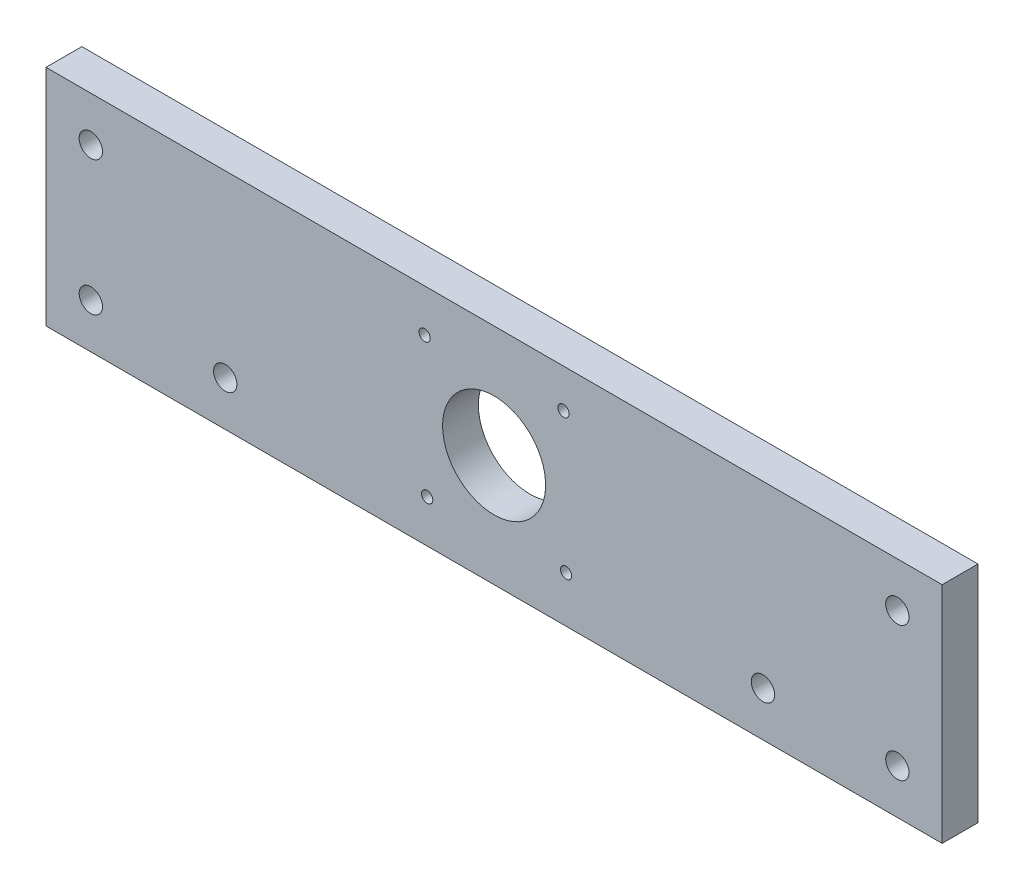
SolidWorks part; units mm, degrees
ref_plane "Ön Düzlem" through (0, 0, 0) normal (0, 0, 1) x (1, 0, 0)
ref_plane "Üst Düzlem" through (0, 0, 0) normal (0, 1, 0) x (1, 0, 0)
ref_plane "Sağ Düzlem" through (0, 0, 0) normal (1, 0, 0) x (0, 0, -1)
sketch "Çizim1" plane through (0, 0, 0) normal (0, 0, 1) x (1, 0, 0)
  line L1 (-88.1446, 49.1848) -> (111.8554, 49.1848)
  line L2 (-88.1446, 49.1848) -> (-88.1446, -0.8152)
  line L3 (-88.1446, -0.8152) -> (111.8554, -0.8152)
  line L4 (111.8554, 49.1848) -> (111.8554, -0.8152)
  circle A3 centre (-78.1446, 39.1848) radius 4.0251
  circle A4 centre (101.8554, 39.1848) radius 4.0251
  circle A5 centre (101.8554, 9.1848) radius 4.0251
  circle A6 centre (-78.1446, 9.1848) radius 4.0251
  dimension "D3" = 10
  dimension "D4" = 10
  dimension "D5" = 2
  dimension "D6" = 2
  dimension "D1" = 200
  dimension "D2" = 50
extrude "Yükseklik-Ekstrüzyon1" add sketch "Çizim1" along normal blind 8 contours L2 L1 L4 L3
hole_wizard "M5 Helisarmal için Zıvana matkabı1" positions "Çizim3" profile "Çizim4" hole size "M5x0.8" standard "ANSI Metric" end condition up to next
sketch "Çizim3" plane through (0, 0, 0) normal (0, 0, -1) x (-1, 0, 0)
  point P0 (-101.8554, 39.1848)
  point P3 (-101.8554, 9.1848)
  point P6 (78.1446, 9.1848)
  point P9 (78.1446, 39.1848)
sketch "Çizim4" plane through (101.8554, 39.1848, 0) normal (1, 0, 0) x (0, 1, 0)
  line L0 (0, 0) -> (0, 8)
  line L1 (0, 8) -> (2.6, 8)
  line L2 (2.6, 8) -> (2.6, 0)
  line L5 (2.6, 0) -> (0, 0)
  line L11 (0, -6.35) -> (0, 107.95) construction
  dimension "Thru Hole Dia." = 5.2
  dimension "Thru Hole Depth" = 8
sketch "Çizim5" plane through (0, 0, 0) normal (0, 0, -1) x (-1, 0, 0)
  circle A1 centre (3.6446, 39.6848) radius 1.25
  circle A2 centre (3.0759, 8.6848) radius 1.25
  circle A3 centre (-27.9241, 9.5445) radius 1.25
  circle A4 centre (-27.3554, 40.5445) radius 1.25
  circle A5 centre (-11.8554, 24.1848) radius 11.5
extrude "Kes-Ekstrüzyon1" cut sketch "Çizim5" against normal blind 10 and the other way blind 10
sketch "Çizim6" plane through (0, 0, 0) normal (0, 0, -1) x (-1, 0, 0)
  line L0 (88.1446, -0.8152) -> (-111.8554, -0.8152) construction
  line L1 (-111.8554, 49.1848) -> (-111.8554, -0.8152) construction
  line L2 (88.1446, 49.1848) -> (88.1446, -0.8152) construction
  circle A0 centre (-71.8554, 9.1848) radius 3.103
  circle A1 centre (48.1446, 9.1848) radius 2.2755
  dimension "D1" = 10
  dimension "D2" = 40
  dimension "D3" = 10
  dimension "D4" = 40
hole_wizard "M5 Helisarmal için Zıvana matkabı2" positions "3B Çizim2" profile "Çizim7" hole size "M5x0.8" standard "ANSI Metric" end condition up to next
sketch3d "3B Çizim2"
  point P0 (71.8554, 9.1848, 0)
  point P3 (-48.1446, 9.1848, 0)
sketch "Çizim7" plane through (71.8554, 9.1848, 0) normal (1, 0, 0) x (0, 1, 0)
  line L0 (0, 0) -> (0, 8)
  line L1 (0, 8) -> (2.6, 8)
  line L2 (2.6, 8) -> (2.6, 0)
  line L5 (2.6, 0) -> (0, 0)
  line L11 (0, -6.35) -> (0, 107.95) construction
  dimension "Thru Hole Dia." = 5.2
  dimension "Thru Hole Depth" = 8
